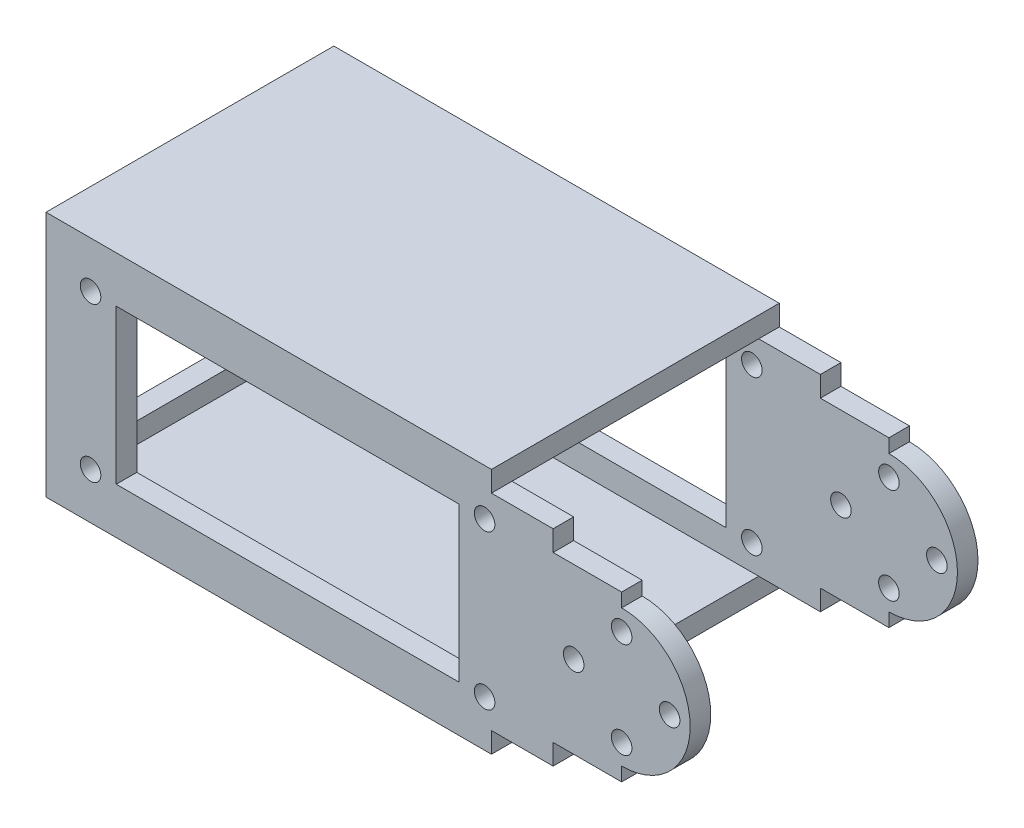
SolidWorks part; units mm, degrees
ref_plane "Front Plane" through (0, 0, 0) normal (0, 0, 1) x (1, 0, 0)
ref_plane "Top Plane" through (0, 0, 0) normal (0, 1, 0) x (1, 0, 0)
ref_plane "Right Plane" through (0, 0, 0) normal (1, 0, 0) x (0, 0, -1)
sketch "Sketch1" plane through (0, 0, 0) normal (0, 0, 1) x (1, 0, 0)
  line L0 (0, 10) -> (0, 12)
  line L1 (-10, 15) -> (-81, 15)
  line L2 (-81, 15) -> (-81, -15)
  line L3 (-81, -15) -> (-10, -15)
  line L4 (0, -12) -> (0, -10)
  line L5 (-10, 15) -> (-10, 12)
  line L6 (-10, 12) -> (0, 12)
  line L7 (-10, -15) -> (-10, -12)
  line L8 (-10, -12) -> (0, -12)
  line L10 (-73.75, 11.25) -> (-23.75, 11.25)
  line L11 (-73.75, 11.25) -> (-73.75, -11.25)
  line L12 (-73.75, -11.25) -> (-23.75, -11.25)
  line L13 (-23.75, 11.25) -> (-23.75, -11.25)
  line L14 (-73.75, 11.25) -> (-23.75, -11.25) construction
  line L15 (-73.75, -11.25) -> (-23.75, 11.25) construction
  arc A0 (0, -10) -> (0, 10) centre (0, 0) ccw
  circle A1 centre (0, 7) radius 1.5
  circle A2 centre (7, 0) radius 1.5
  circle A3 centre (0, -7) radius 1.5
  circle A4 centre (-7, 0) radius 1.5
  circle A7 centre (-20, 11.25) radius 1.5
  circle A8 centre (-20, -11.25) radius 1.5
  circle A13 centre (-77.5, 11.25) radius 1.5
  circle A14 centre (-77.5, -11.25) radius 1.5
  point P14 (0, 0)
  point P17 (-48.75, 0)
  dimension "D1" = 20
  dimension "D2" = 7
  dimension "D10" = 22.5
  dimension "D11" = 3
  dimension "D12" = 3
  dimension "D13" = 3.75
  dimension "D14" = 3
  dimension "D15" = 3
  dimension "D21" = 3
  dimension "D4" = 2
  dimension "D5" = 3
  dimension "D6" = 3
  dimension "D7" = 2
  dimension "D8" = 10
  dimension "D9" = 10
  dimension "D16" = 57.5
  dimension "D17" = 71
  dimension "D18" = 50
  dimension "D19" = 22.5
  dimension "D20" = 3.75
  dimension "D3" = 4
extrude "Boss-Extrude2" add sketch "Sketch1" along normal blind 3
sketch "Sketch2" plane through (-81, 0, 0) normal (-1, 0, 0) x (0, 0, 1)
  line L1 (0, 15) -> (42, 15)
  line L2 (0, 15) -> (0, -15)
  line L3 (0, -15) -> (42, -15)
  line L4 (42, 15) -> (42, -15)
  dimension "D1" = 42
extrude "Boss-Extrude3" add sketch "Sketch2" along normal blind 3
extrude "Boss-Extrude4" add sketch "Sketch1<2>" along normal blind 3 from offset 39
sketch "Sketch1<2>" plane through (0, 0, 0) normal (0, 0, 1) x (1, 0, 0) same geometry as "Sketch1"
sketch "Sketch4" plane through (-84, 0, 0) normal (-1, 0, 0) x (0, 0, 1)
  line L1 (3, 12) -> (39, 12)
  line L2 (3, 12) -> (3, -12)
  line L3 (3, -12) -> (39, -12)
  line L4 (39, 12) -> (39, -12)
  line L5 (3, 12) -> (39, -12) construction
  line L6 (3, -12) -> (39, 12) construction
  point P0 (21, 0)
  point P5 (0, 0)
  point P7 (42.5178, 15.5278)
  dimension "D1" = 36
  dimension "D2" = 24
  dimension "D3" = 3
  dimension "D4" = 3
extrude "Cut-Extrude1" cut sketch "Sketch4" against normal blind 3
sketch "Sketch5" plane through (0, 15, 0) normal (0, 1, 0) x (1, 0, 0)
  line L0 (-84, -42) -> (-10, -42) construction
  line L1 (-84, 0) -> (-19, 0)
  line L2 (-84, 0) -> (-84, -42)
  line L3 (-84, -42) -> (-19, -42)
  line L4 (-19, 0) -> (-19, -42)
  dimension "D1" = 65
extrude "Boss-Extrude5" add sketch "Sketch5" along normal blind 3
sketch "Sketch6" plane through (0, -15, 0) normal (0, -1, 0) x (1, 0, 0)
  line L1 (-84, 42) -> (-19, 42)
  line L2 (-84, 42) -> (-84, 0)
  line L3 (-84, 0) -> (-19, 0)
  line L4 (-19, 42) -> (-19, 0)
extrude "Boss-Extrude6" add sketch "Sketch6" along normal blind 3
